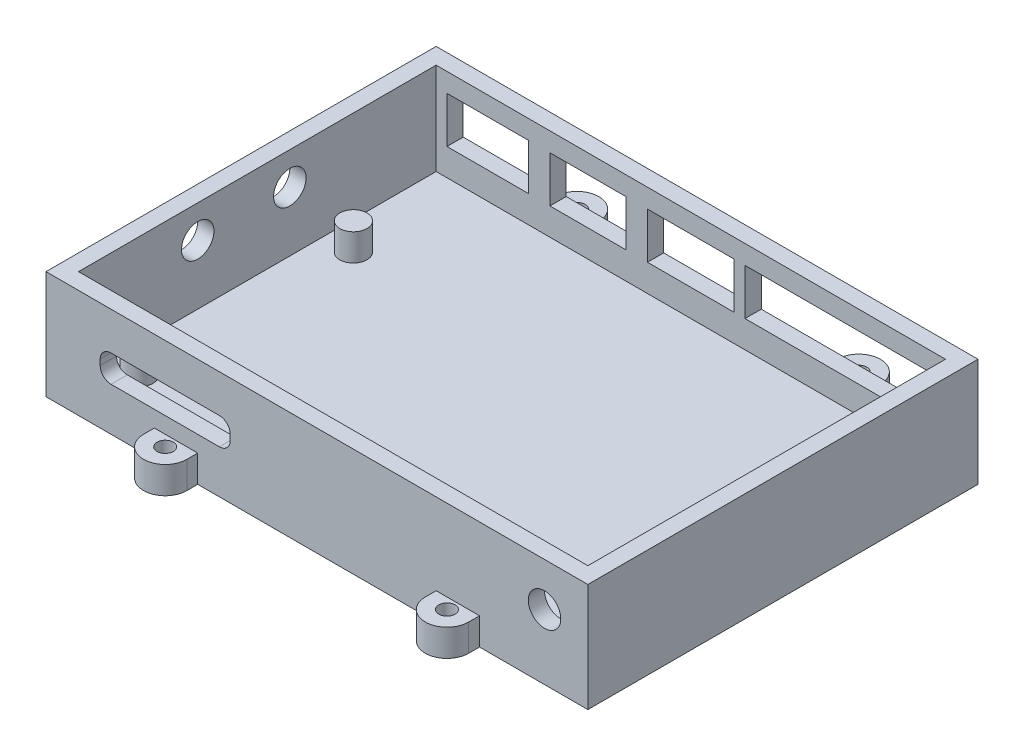
SolidWorks part; units mm, degrees
ref_plane "Front" through (0, 0, 0) normal (0, 0, 1) x (1, 0, 0)
ref_plane "Top" through (0, 0, 0) normal (0, 1, 0) x (1, 0, 0)
ref_plane "Right" through (0, 0, 0) normal (1, 0, 0) x (0, 0, -1)
sketch "Sketch1" plane through (0, 0, 0) normal (0, 1, 0) x (1, 0, 0)
  line L1 (-49.1968, 43.2851) -> (50.8032, 43.2851)
  line L2 (-49.1968, 43.2851) -> (-49.1968, -28.7149)
  line L3 (-49.1968, -28.7149) -> (50.8032, -28.7149)
  line L4 (50.8032, 43.2851) -> (50.8032, -28.7149)
  dimension "D1" = 100
  dimension "D2" = 72
extrude "Boss-Extrude1" add sketch "Sketch1" along normal blind 20
sketch "Sketch2" plane through (0, 20, 0) normal (0, 1, 0) x (1, 0, 0)
  line L0 (50.8032, 43.2851) -> (-49.1968, 43.2851) construction
  line L1 (-46.1968, 40.2851) -> (47.8032, 40.2851)
  line L2 (-46.1968, 40.2851) -> (-46.1968, -25.7149)
  line L3 (-46.1968, -25.7149) -> (47.8032, -25.7149)
  line L4 (47.8032, 40.2851) -> (47.8032, -25.7149)
  line L5 (-49.1968, 43.2851) -> (-49.1968, -28.7149) construction
  line L6 (-49.1968, -28.7149) -> (50.8032, -28.7149) construction
  line L7 (50.8032, -28.7149) -> (50.8032, 43.2851) construction
  dimension "D1" = 3
  dimension "D2" = 3
  dimension "D3" = 3
  dimension "D4" = 3
extrude "Cut-Extrude1" cut sketch "Sketch2" against normal blind 17
sketch "Sketch3" plane through (0, 3, 0) normal (0, 1, 0) x (1, 0, 0)
  line L0 (-46.1968, -25.7149) -> (47.8032, -25.7149) construction
  line L1 (-46.1968, -25.7149) -> (47.8032, -25.7149) construction
  line L2 (47.8032, 40.2851) -> (-46.1968, 40.2851) construction
  circle A0 centre (-40.9628, -19.7149) radius 2.5
  circle A1 centre (-40.9628, 19.7851) radius 2.5
  circle A2 centre (43.0372, -17.7149) radius 2.5
  circle A3 centre (43.0372, 19.7851) radius 2.5
  dimension "D1" = 5
  dimension "D3" = 5
  dimension "D4" = 5
  dimension "D9" = 5
  dimension "D2" = 6
  dimension "D5" = 8
  dimension "D6" = 84
  dimension "D7" = 39.5
  dimension "D8" = 20.5
  dimension "D10" = 84
  dimension "D11" = 37.5
extrude "Boss-Extrude2" add sketch "Sketch3" along normal blind 5
sketch "Sketch6" plane through (0, 0, -43.2851) normal (0, 0, -1) x (-1, 0, 0)
  line L1 (-46.8032, 16.5) -> (-10.8032, 16.5)
  line L2 (-46.8032, 16.5) -> (-46.8032, 8)
  line L3 (-46.8032, 8) -> (-10.8032, 8)
  line L4 (-10.8032, 16.5) -> (-10.8032, 8)
  line L19 (11.1968, 16.5) -> (25.1968, 16.5)
  line L20 (11.1968, 16.5) -> (11.1968, 8)
  line L21 (11.1968, 8) -> (25.1968, 8)
  line L22 (25.1968, 16.5) -> (25.1968, 8)
  line L23 (-8.8032, 16.5) -> (7.1968, 16.5)
  line L24 (-8.8032, 16.5) -> (-8.8032, 8)
  line L25 (-8.8032, 8) -> (7.1968, 8)
  line L26 (7.1968, 16.5) -> (7.1968, 8)
  line L27 (29.1968, 16.5) -> (44.1968, 16.5)
  line L28 (29.1968, 16.5) -> (29.1968, 8)
  line L29 (29.1968, 8) -> (44.1968, 8)
  line L30 (44.1968, 16.5) -> (44.1968, 8)
  line L31 (-50.8032, 20) -> (-50.8032, 0) construction
  line L32 (-50.8032, 20) -> (49.1968, 20) construction
  line L33 (-50.8032, 0) -> (49.1968, 0) construction
  dimension "D1" = 4
  dimension "D2" = 40
  dimension "D3" = 42
  dimension "D4" = 58
  dimension "D5" = 62
  dimension "D6" = 76
  dimension "D7" = 80
  dimension "D8" = 95
  dimension "D9" = 3.5
  dimension "D10" = 8
extrude "Boss-Extrude4" add sketch "Sketch6" against normal blind 12 contours L26 L23 L24 L25 | L22 L19 L20 L21 | L30 L27 L28 L29 | L2 L1 L4 L3 region at (-18.1968, 12.25, -43.2851) region at (0.8032, 12.25, -43.2851) region at (-36.6968, 12.25, -43.2851)
extrude "Cut-Extrude2" cut sketch "Sketch6<6>" against normal blind 18
sketch "Sketch6<6>" plane through (0, 0, -43.2851) normal (0, 0, -1) x (-1, 0, 0) same geometry as "Sketch6"
sketch "usb type-c" plane through (0, 0, 28.7149) normal (0, 0, 1) x (1, 0, 0)
  line L0 (-49.1968, 20) -> (-49.1968, 0) construction
  line L1 (-37.1968, 13) -> (-17.1968, 13)
  line L2 (-39.1968, 11) -> (-39.1968, 10)
  line L3 (-37.1968, 8) -> (-17.1968, 8)
  line L4 (-15.1968, 11) -> (-15.1968, 10)
  line L5 (-49.1968, 20) -> (50.8032, 20) construction
  arc A0 (-17.1968, 8) -> (-15.1968, 10) centre (-17.1968, 10) ccw
  arc A1 (-17.1968, 13) -> (-15.1968, 11) centre (-17.1968, 11) cw
  arc A2 (-39.1968, 10) -> (-37.1968, 8) centre (-37.1968, 10) ccw
  arc A3 (-37.1968, 13) -> (-39.1968, 11) centre (-37.1968, 11) ccw
  point P4 (-39.1968, 10.5)
  point P7 (-15.1968, 10.5)
  point P8 (-27.1968, 8)
  point P11 (-27.1968, 13)
  dimension "D5" = 2
  dimension "D1" = 10
  dimension "D2" = 34
  dimension "D3" = 12
  dimension "D4" = 7
extrude "Cut-Extrude4" cut sketch "usb type-c" against normal blind 18
sketch "ant1-hole" plane through (-49.1968, 0, 0) normal (-1, 0, 0) x (0, 0, 1)
  line L2 (-43.2851, 20) -> (28.7149, 20) construction
  line L3 (-43.2851, 20) -> (-43.2851, 0) construction
  circle A0 centre (-13.2851, 14) radius 3
  dimension "D1" = 6
  dimension "D2" = 30
sketch "ant2-hole" plane through (-49.1968, 0, 0) normal (-1, 0, 0) x (0, 0, 1)
  line L0 (-43.2851, 20) -> (28.7149, 20) construction
  line L1 (28.7149, 20) -> (28.7149, 0) construction
  circle A0 centre (3.7149, 14) radius 3
  dimension "D1" = 6
  dimension "D2" = 25
extrude "Cut-Extrude5" cut sketch "ant1-hole" against normal blind 10
extrude "Cut-Extrude6" cut sketch "ant2-hole" against normal blind 10
sketch "reset-hole" plane through (0, 0, 28.7149) normal (0, 0, 1) x (1, 0, 0)
  line L1 (50.8032, 20) -> (50.8032, 0) construction
  line L2 (-49.1968, 20) -> (50.8032, 20) construction
  circle A0 centre (42.8032, 12) radius 3
  dimension "D1" = 8
  dimension "D2" = 8
extrude "Cut-Extrude8" cut sketch "reset-hole" against normal blind 6
sketch "lug1" plane through (0, 0, 0) normal (0, 1, 0) x (1, 0, 0)
  line L0 (-29.1968, -28.7149) -> (-29.1968, -30.7149)
  line L1 (-49.1968, -28.7149) -> (50.8032, -28.7149) construction
  line L2 (-21.1968, -28.7149) -> (-29.1968, -28.7149)
  line L3 (-21.1968, -28.7149) -> (-21.1968, -30.7149)
  line L4 (-49.1968, 43.2851) -> (-49.1968, -28.7149) construction
  arc A0 (-29.1968, -30.7149) -> (-21.1968, -30.7149) centre (-25.1968, -30.7149) ccw
  circle A1 centre (-25.1968, -30.7149) radius 1.5
  point P6 (-29.1968, -29.7149)
  dimension "D1" = 8
  dimension "D2" = 2
  dimension "D3" = 20
extrude "Boss-Extrude10" add sketch "lug1" along normal blind 5
sketch "lug2" plane through (0, 0, 0) normal (0, 1, 0) x (1, 0, 0)
  line L0 (22.8032, -28.7149) -> (22.8032, -30.7149)
  line L2 (30.8032, -28.7149) -> (22.8032, -28.7149)
  line L3 (30.8032, -28.7149) -> (30.8032, -30.7149)
  arc A0 (22.8032, -30.7149) -> (30.8032, -30.7149) centre (26.8032, -30.7149) ccw
  circle A1 centre (26.8032, -30.7149) radius 1.5
  dimension "D1" = 8
  dimension "D2" = 2
  dimension "D3" = 20
extrude "Boss-Extrude11" add sketch "lug2" along normal blind 5
sketch "lug3" plane through (0, 0, 0) normal (0, 1, 0) x (1, 0, 0)
  line L0 (30.8032, 43.2709) -> (30.8032, 45.2709)
  line L1 (22.8032, 43.2709) -> (30.8032, 43.2709)
  line L2 (22.8032, 43.2709) -> (22.8032, 45.2709)
  arc A0 (30.8032, 45.2709) -> (22.8032, 45.2709) centre (26.8032, 45.2709) ccw
  circle A1 centre (26.8032, 45.2709) radius 1.5
  point P6 (0, 0)
  dimension "D1" = 20
sketch "lug4" plane through (0, 0, 0) normal (0, 1, 0) x (1, 0, 0)
  line L0 (-21.1968, 43.2851) -> (-21.1968, 45.2851)
  line L1 (-29.1968, 43.2851) -> (-21.1968, 43.2851)
  line L2 (-29.1968, 43.2851) -> (-29.1968, 45.2851)
  arc A0 (-21.1968, 45.2851) -> (-29.1968, 45.2851) centre (-25.1968, 45.2851) ccw
  circle A1 centre (-25.1968, 45.2851) radius 1.5
  dimension "D1" = 20
extrude "Boss-Extrude12" add sketch "lug3" along normal blind 5
extrude "Boss-Extrude13" add sketch "lug4" along normal blind 5
